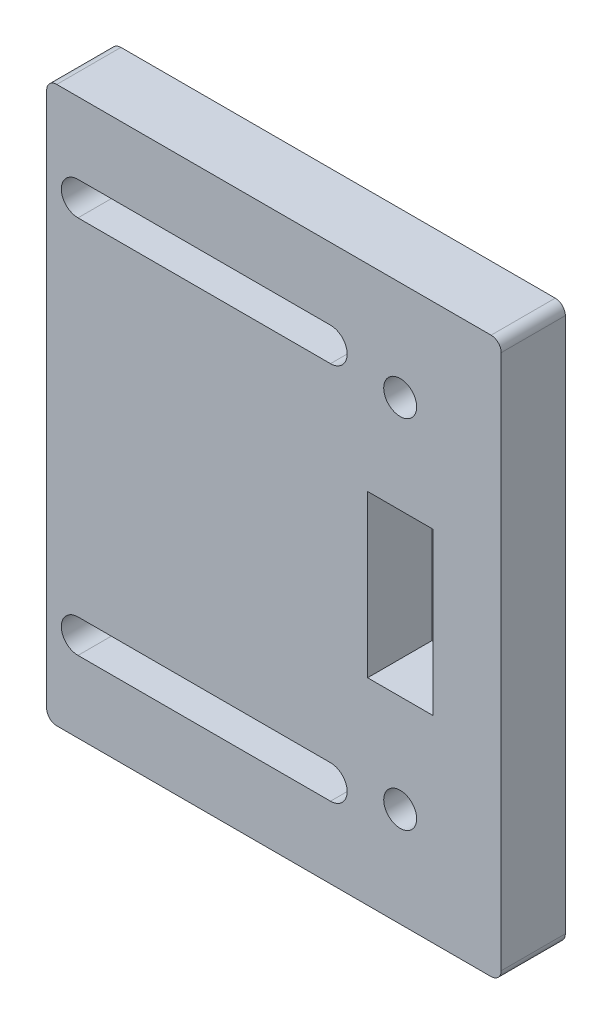
SolidWorks part; units mm, degrees
ref_plane "Front Plane" through (0, 0, 0) normal (0, 0, 1) x (1, 0, 0)
ref_plane "Top Plane" through (0, 0, 0) normal (0, 1, 0) x (1, 0, 0)
ref_plane "Right Plane" through (0, 0, 0) normal (1, 0, 0) x (0, 0, -1)
sketch "Sketch1" plane through (0, 0, 0) normal (0, 0, 1) x (1, 0, 0)
  line L0 (70, -110) -> (70, -90.31) construction
  line L1 (0, 0) -> (90, 0)
  line L2 (0, 0) -> (0, -110)
  line L3 (0, -110) -> (90, -110)
  line L4 (90, 0) -> (90, -110)
  line L6 (70, -39.0256) -> (76.45, -39.0256)
  line L8 (76.45, -70.9756) -> (70, -70.9756)
  line L9 (70, -70.9756) -> (63.55, -70.9756)
  line L10 (63.55, -70.9756) -> (63.55, -39.0256)
  line L11 (63.55, -39.0256) -> (70, -39.0256)
  line L12 (80, 0) -> (80, -19.69) construction
  line L14 (76.45, -39.0256) -> (76.45, -55.0006)
  line L15 (76.45, -55.0006) -> (76.45, -70.9756)
  dimension "D6" = 10
  dimension "D1" = 110
  dimension "D2" = 31.95
  dimension "D3" = 12.9
  dimension "D4" = 19.69
  dimension "D5" = 19.69
  dimension "D7" = 90
  dimension "D8" = 80
  dimension "D9" = 13.55
  dimension "D10" = 39.0244
  dimension "D11" = 10
  dimension "D12" = 10
extrude "Boss-Extrude2" add sketch "Sketch1" along normal blind 12.7
sketch "Sketch8" plane through (0, 0, 0) normal (0, 0, -1) x (-1, 0, 0)
  line L1 (-70, -110) -> (-70, -90.31) construction
  dimension "D1" = 19.69
  dimension "D2" = 20
hole_wizard "CSK for 1/4 Flat Head Machine Screw3" positions "Sketch9" profile "Sketch10" countersink size "1/4" standard "ANSI Inch" end condition through all
sketch "Sketch9" plane through (0, 0, 0) normal (0, 0, -1) x (-1, 0, 0)
  point P0 (-70, -90.31)
sketch "Sketch10" plane through (70, -90.31, 0) normal (1, 0, 0) x (0, 1, 0)
  line L0 (0, 0) -> (0, 12.7)
  line L1 (0, 12.7) -> (3.2639, 12.7)
  line L2 (3.2639, 12.7) -> (3.2639, 3.6524)
  line L3 (3.2639, 3.6524) -> (6.4389, 0)
  line L5 (6.4389, 0) -> (0, 0)
  line L6 (-3.2639, 3.6524) -> (-6.4389, 0) construction
  line L11 (0, -6.35) -> (0, 107.95) construction
  dimension "Thru Hole Dia." = 6.5278
  dimension "Thru Hole Depth" = 12.7
  dimension "Near C'Sink Dia." = 12.8778
  dimension "Near C'Sink Angle" = 82
sketch "Sketch11" plane through (0, 0, 0) normal (0, 0, -1) x (-1, 0, 0)
  line L0 (-70, 0) -> (-70, -19.69)
  dimension "D1" = 19.69
  dimension "D2" = 20
hole_wizard "CSK for 1/4 Flat Head Machine Screw4" positions "Sketch12" profile "Sketch13" countersink size "1/4" standard "ANSI Inch" end condition through all
sketch "Sketch12" plane through (0, 0, 0) normal (0, 0, -1) x (-1, 0, 0)
  point P0 (-70, -19.69)
sketch "Sketch13" plane through (70, -19.69, 0) normal (1, 0, 0) x (0, 1, 0)
  line L0 (0, 0) -> (0, 12.7)
  line L1 (0, 12.7) -> (3.2639, 12.7)
  line L2 (3.2639, 12.7) -> (3.2639, 3.6524)
  line L3 (3.2639, 3.6524) -> (6.4389, 0)
  line L5 (6.4389, 0) -> (0, 0)
  line L6 (-3.2639, 3.6524) -> (-6.4389, 0) construction
  line L11 (0, -6.35) -> (0, 107.95) construction
  dimension "Thru Hole Dia." = 6.5278
  dimension "Thru Hole Depth" = 12.7
  dimension "Near C'Sink Dia." = 12.8778
  dimension "Near C'Sink Angle" = 82
fillet "Fillet1" radius 2 4 edges at (0, 0, 6.35) (90, 0, 6.35) (0, -110, 6.35) (90, -110, 6.35)
sketch "Sketch15" plane through (0, 0, 0) normal (0, 0, -1) x (-1, 0, 0)
  line L0 (-56.2003, -14.185) -> (-6.2003, -14.185)
  line L1 (-56.2003, -20.785) -> (-6.2003, -20.785)
  line L2 (0, -55) -> (-82.6046, -55) construction
  line L3 (0, -2) -> (0, -108) construction
  line L4 (-56.2003, -89.215) -> (-6.2003, -89.215)
  line L5 (-56.2003, -95.815) -> (-6.2003, -95.815)
  arc A0 (-6.2003, -14.185) -> (-6.2003, -20.785) centre (-6.2003, -17.485) cw
  arc A1 (-56.2003, -20.785) -> (-56.2003, -14.185) centre (-56.2003, -17.485) cw
  arc A2 (-6.2003, -95.815) -> (-6.2003, -89.215) centre (-6.2003, -92.515) ccw
  arc A3 (-56.2003, -89.215) -> (-56.2003, -95.815) centre (-56.2003, -92.515) ccw
  dimension "D3" = 3.3
  dimension "D4" = 68.43
  dimension "D1" = 50
  dimension "D2" = 50
extrude "Cut-Extrude1" cut sketch "Sketch15" against normal through all
